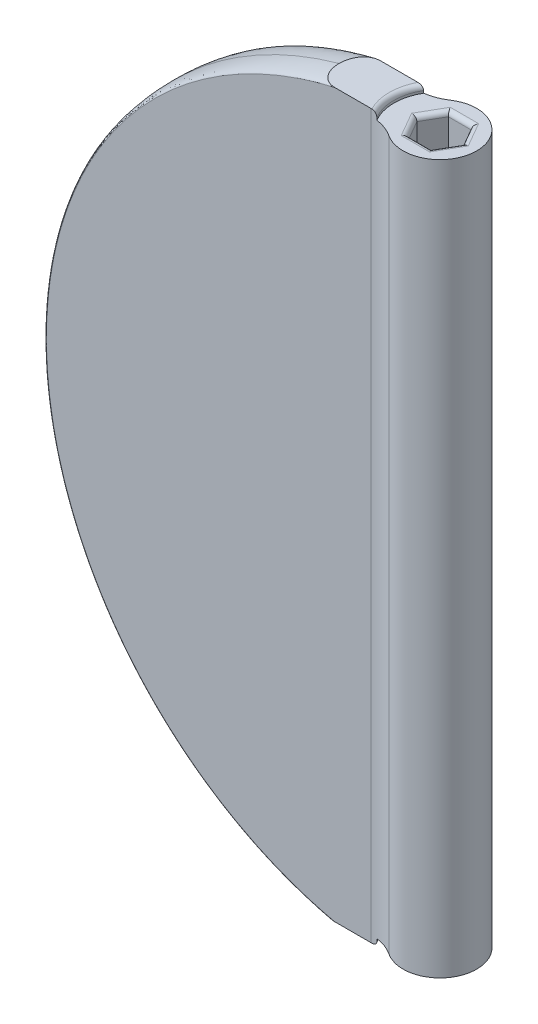
SolidWorks part; units mm, degrees
ref_plane "Front Plane" through (0, 0, 0) normal (0, 0, 1) x (1, 0, 0)
ref_plane "Top Plane" through (0, 0, 0) normal (0, 1, 0) x (1, 0, 0)
ref_plane "Right Plane" through (0, 0, 0) normal (1, 0, 0) x (0, 0, -1)
sketch "Sketch1" plane through (0, 0, 0) normal (0, 0, 1) x (1, 0, 0)
  line L0 (0, 78.5) -> (0, -78.5)
  line L5 (-21.9089, 78.5) -> (0, 78.5)
  line L6 (-21.9089, 78.5) -> (-21.9089, -78.5) construction
  line L7 (-21.9089, -78.5) -> (0, -78.5)
  line L8 (21.9089, 78.5) -> (21.9089, -78.5) construction
  line L9 (-21.9089, 78.5) -> (21.9089, -78.5) construction
  line L10 (-21.9089, -78.5) -> (21.9089, 78.5) construction
  line L11 (0, 78.5) -> (21.9089, 78.5) construction
  line L12 (0, -78.5) -> (21.9089, -78.5) construction
  arc A0 (-21.9089, 78.5) -> (-21.9089, -78.5) centre (0, 0) ccw
  arc A1 (21.9089, 78.5) -> (-21.9089, 78.5) centre (0, 0) ccw construction
  arc A2 (21.9089, -78.5) -> (21.9089, 78.5) centre (0, 0) ccw construction
  arc A3 (-21.9089, -78.5) -> (21.9089, -78.5) centre (0, 0) ccw construction
  dimension "D1" = 163
  dimension "D2" = 157
extrude "Boss-Extrude1" add sketch "Sketch1" along normal mid plane 10
sketch "Sketch2" plane through (0, 78.5, 0) normal (0, 1, 0) x (1, 0, 0)
  circle A0 centre (0, 0) radius 8
  dimension "D1" = 16
extrude "Boss-Extrude2" add sketch "Sketch2" against normal up to surface (157 mm away) up to face at (-10.9545, -78.5, 0)
fillet "Fillet1" radius 10 2 edges at (-6.245, 0, -5) (-6.245, 0, 5)
sketch "Sketch3" plane through (0, -78.5, 0) normal (0, -1, 0) x (1, 0, 0)
  line L1 (2.5, -4.3301) -> (5, 0)
  line L2 (5, 0) -> (2.5, 4.3301)
  line L3 (2.5, 4.3301) -> (-2.5, 4.3301)
  line L4 (-2.5, 4.3301) -> (-5, 0)
  line L5 (-5, 0) -> (-2.5, -4.3301)
  line L6 (-2.5, -4.3301) -> (2.5, -4.3301)
  circle A0 centre (0, 0) radius 5 construction
  circle A1 centre (0, 0) radius 4.3301 construction
  point P3 (0, 0)
  dimension "D1" = 10
extrude "Cut-Extrude1" cut sketch "Sketch3" against normal blind 30
sketch "Sketch5" plane through (0, -78.5, 0) normal (0, -1, 0) x (1, 0, 0)
  circle A0 centre (0, 0) radius 10
  dimension "D1" = 20
extrude "Cut-Extrude2" cut sketch "Sketch5" against normal blind 1.5
mirror "Mirror1" about plane through (0, 0, 0) normal (0, 1, 0) of "Cut-Extrude2", "Cut-Extrude1"
fillet "Fillet2" radius 1 2 edges at (-81.5, 0, 5) (-81.5, 0, -5) second distance 5 first distance on face at (-30.8272, 0, 5) first distance on face at (-30.8272, 0, -5)
fillet "Fillet4" radius 1 14 edges at (-10, 78.5, 0) (-10, -78.5, 0) (3.75, 77, 2.1651) (3.75, 77, -2.1651) (0, 77, -4.3301) (-3.75, 77, -2.1651) (-3.75, 77, 2.1651) (0, 77, 4.3301) (3.75, -77, 2.1651) (3.75, -77, -2.1651) (0, -77, -4.3301) (-3.75, -77, -2.1651) (-3.75, -77, 2.1651) (0, -77, 4.3301)
